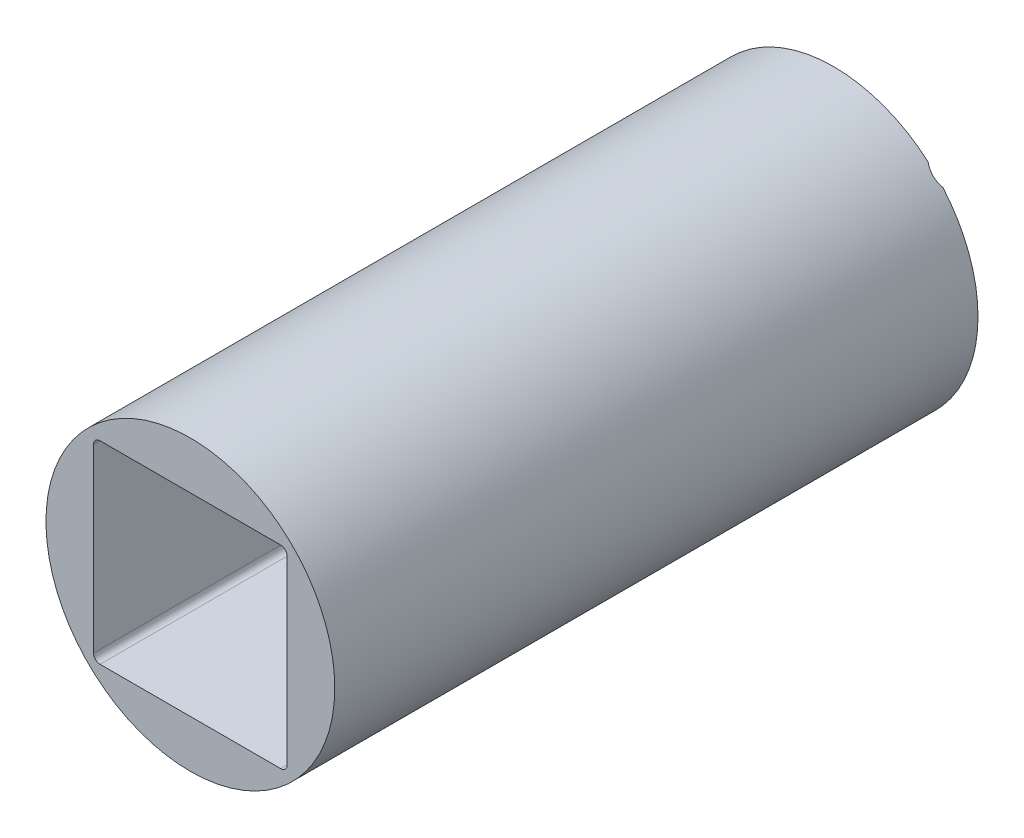
SolidWorks part; units mm, degrees
ref_plane "Ebene vorne" through (0, 0, 0) normal (0, 0, 1) x (1, 0, 0)
ref_plane "Ebene oben" through (0, 0, 0) normal (0, 1, 0) x (1, 0, 0)
ref_plane "Ebene rechts" through (0, 0, 0) normal (1, 0, 0) x (0, 0, -1)
sketch "Skizze1" plane through (0, 0, 0) normal (0, 0, 1) x (1, 0, 0)
  line L1 (-15.05, 15.05) -> (15.05, 15.05)
  line L2 (-15.05, 15.05) -> (-15.05, -15.05)
  line L3 (-15.05, -15.05) -> (15.05, -15.05)
  line L4 (15.05, 15.05) -> (15.05, -15.05)
  line L5 (-15.05, 15.05) -> (15.05, -15.05) construction
  line L6 (-15.05, -15.05) -> (15.05, 15.05) construction
  circle A0 centre (0, 0) radius 22.45
  dimension "D1" = 44.9
  dimension "D2" = 30.1
  dimension "D3" = 30.1
extrude "Aufsatz-Linear austragen1" add sketch "Skizze1" along normal blind 100
fillet "Verrundung1" radius 1 4 edges at (-15.05, -15.05, 50) (15.05, -15.05, 50) (15.05, 15.05, 50) (-15.05, 15.05, 50)
chamfer "Fase1" distance 2 angle 45 8 edges at (0, -15.05, 0) (14.7571, -14.7571, 0) (-14.7571, -14.7571, 0) (15.05, 0, 0) (-15.05, 0, 0) (14.7571, 14.7571, 0) (-14.7571, 14.7571, 0) (0, 15.05, 0)
